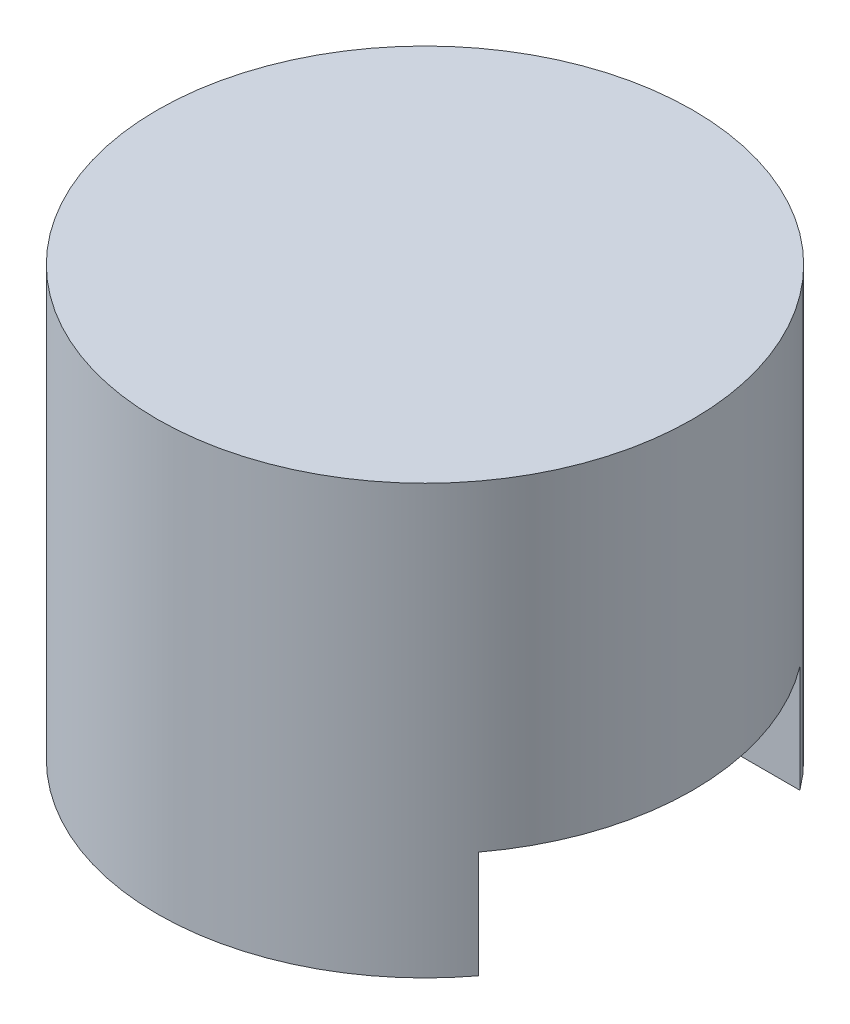
SolidWorks part; units mm, degrees
ref_plane "Front Plane" through (0, 0, 0) normal (0, 0, 1) x (1, 0, 0)
ref_plane "Top Plane" through (0, 0, 0) normal (0, 1, 0) x (1, 0, 0)
ref_plane "Right Plane" through (0, 0, 0) normal (1, 0, 0) x (0, 0, -1)
sketch "Sketch1" plane through (0, 0, 0) normal (0, 1, 0) x (1, 0, 0)
  circle A0 centre (0, 0) radius 15.875
  dimension "D1" = 31.75
extrude "Boss-Extrude1" add sketch "Sketch1" along normal blind 25.4
sketch "Sketch2" plane through (0, 0, 0) normal (1, 0, 0) x (0, 0, -1)
  line L1 (-9.525, -6.35) -> (9.525, -6.35)
  line L2 (-9.525, -6.35) -> (-9.525, 6.35)
  line L3 (-9.525, 6.35) -> (9.525, 6.35)
  line L4 (9.525, -6.35) -> (9.525, 6.35)
  line L5 (-9.525, -6.35) -> (9.525, 6.35) construction
  line L6 (-9.525, 6.35) -> (9.525, -6.35) construction
  point P0 (0, 0)
  dimension "D1" = 19.05
  dimension "D2" = 12.7
extrude "Cut-Extrude1" cut sketch "Sketch2" against normal through all and the other way through all
